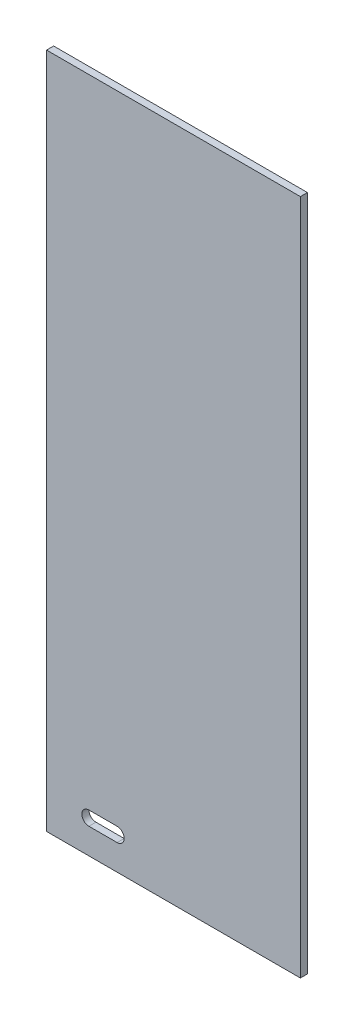
SolidWorks part; units mm, degrees
ref_plane "Front Plane" through (0, 0, 0) normal (0, 0, 1) x (1, 0, 0)
ref_plane "Top Plane" through (0, 0, 0) normal (0, 1, 0) x (1, 0, 0)
ref_plane "Right Plane" through (0, 0, 0) normal (1, 0, 0) x (0, 0, -1)
sketch "Sketch1" plane through (0, 0, 0) normal (0, 0, 1) x (1, 0, 0)
  line L1 (0, 0) -> (-228.6, 0)
  line L2 (0, 0) -> (0, 609.6)
  line L3 (0, 609.6) -> (-228.6, 609.6)
  line L4 (-228.6, 0) -> (-228.6, 609.6)
  dimension "D1" = 228.6
  dimension "D2" = 609.6
extrude "Boss-Extrude1" add sketch "Sketch1" along normal blind 6.35
sketch "Sketch2" plane through (0, 0, 6.35) normal (0, 0, 1) x (1, 0, 0)
  line L0 (-165.0954, 29.4853) -> (-190.4954, 29.4853) construction
  line L1 (-165.0954, 23.1353) -> (-190.4954, 23.1353)
  line L2 (-165.0954, 35.8353) -> (-190.4954, 35.8353)
  arc A0 (-165.0954, 23.1353) -> (-165.0954, 35.8353) centre (-165.0954, 29.4853) ccw
  arc A1 (-190.4954, 35.8353) -> (-190.4954, 23.1353) centre (-190.4954, 29.4853) ccw
  point P2 (-177.7954, 29.4853)
extrude "Cut-Extrude1" cut sketch "Sketch2" against normal blind 6.35
